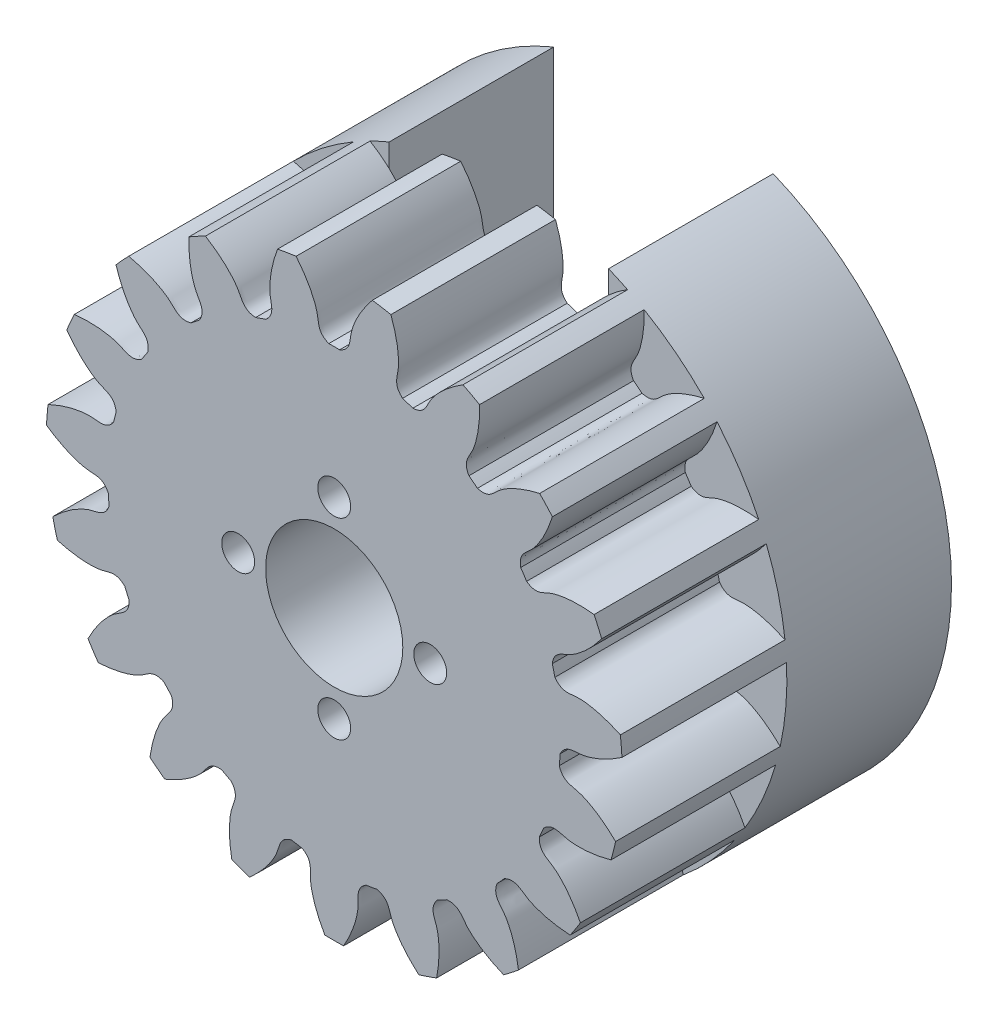
SolidWorks part; units mm, degrees
ref_plane "前视基准面" through (0, 0, 0) normal (0, 0, 1) x (1, 0, 0)
ref_plane "上视基准面" through (0, 0, 0) normal (0, 1, 0) x (1, 0, 0)
ref_plane "右视基准面" through (0, 0, 0) normal (1, 0, 0) x (0, 0, -1)
sketch "草图1" plane through (0, 0, 0) normal (0, 0, 1) x (1, 0, 0)
  circle A0 centre (0, 0) radius 52.5
extrude "凸台-拉伸1" add sketch "草图1" along normal blind 30
ref_axis "基准轴1" through (0, 0, -1.5) along (0, 0, 1)
sketch "草图2" plane through (0, 0, 0) normal (0, 0, 1) x (1, 0, 0)
  line L0 (0, 0) -> (0, 52.5) construction
  circle A0 centre (0, 0) radius 52.5 construction
  arc A1 (0.9829, 41.2383) -> (-0.9829, 41.2383) centre (0, 0) ccw
  arc A2 (15.3566, 59.3035) -> (-15.3566, 59.3035) centre (0, 0) ccw
  spline S0 degree 3 poles (0.9829, 41.2383) (3.0166, 42.0591) (2.7957, 43.6119) (3.1268, 45.1008) (3.1626, 45.2483) (3.206, 45.4123) (3.2575, 45.5925) (3.3179, 45.7888) (3.3877, 46.0008) (3.4677, 46.2282) (3.5584, 46.4706) (3.6606, 46.7278) (3.7749, 46.9994) (3.9017, 47.2849) (4.0419, 47.5841) (4.1959, 47.8963) (4.3643, 48.2213) (4.5477, 48.5586) (4.7466, 48.9076) (4.9617, 49.2679) (5.1933, 49.639) (5.4421, 50.0203) (5.7085, 50.4113) (5.993, 50.8115) (6.2961, 51.2203) (6.6182, 51.637) (6.9598, 52.0611) (7.3213, 52.492) (7.7031, 52.929) (8.1055, 53.3715) (8.529, 53.8189) (8.9739, 54.2704) (9.4405, 54.7254) (9.9291, 55.1832) (10.4401, 55.643) (10.9736, 56.1042) (11.53, 56.5661) (12.1095, 57.0279) (12.7123, 57.4888) (13.3386, 57.9482) (14.215, 58.5643) (14.8935, 59.0113) (15.3566, 59.3035) knots 0 0 0 0 0.181988 0.187669 0.194107 0.201302 0.209255 0.217965 0.227433 0.237658 0.248641 0.260381 0.272878 0.286133 0.300145 0.314915 0.330442 0.346727 0.363769 0.381568 0.400125 0.419439 0.43951 0.460339 0.481926 0.50427 0.527371 0.55123 0.575846 0.601219 0.62735 0.654238 0.681884 0.710287 0.739448 0.769366 0.800042 0.831474 0.863665 0.896612 0.930318 1 1 1 1
  spline S1 degree 3 poles (-0.9829, 41.2383) (-3.0166, 42.0591) (-2.7957, 43.6119) (-3.1268, 45.1008) (-3.1626, 45.2483) (-3.206, 45.4123) (-3.2575, 45.5925) (-3.3179, 45.7888) (-3.3877, 46.0008) (-3.4677, 46.2282) (-3.5584, 46.4706) (-3.6606, 46.7278) (-3.7749, 46.9994) (-3.9017, 47.2849) (-4.0419, 47.5841) (-4.1959, 47.8963) (-4.3643, 48.2213) (-4.5477, 48.5586) (-4.7466, 48.9076) (-4.9617, 49.2679) (-5.1933, 49.639) (-5.4421, 50.0203) (-5.7085, 50.4113) (-5.993, 50.8115) (-6.2961, 51.2203) (-6.6182, 51.637) (-6.9598, 52.0611) (-7.3213, 52.492) (-7.7031, 52.929) (-8.1055, 53.3715) (-8.529, 53.8189) (-8.9739, 54.2704) (-9.4405, 54.7254) (-9.9291, 55.1832) (-10.4401, 55.643) (-10.9736, 56.1042) (-11.53, 56.5661) (-12.1095, 57.0279) (-12.7123, 57.4888) (-13.3386, 57.9482) (-14.215, 58.5643) (-14.8935, 59.0113) (-15.3566, 59.3035) knots 0 0 0 0 0.181988 0.187669 0.194107 0.201302 0.209255 0.217965 0.227433 0.237658 0.248641 0.260381 0.272878 0.286133 0.300145 0.314915 0.330442 0.346727 0.363769 0.381568 0.400125 0.419439 0.43951 0.460339 0.481926 0.50427 0.527371 0.55123 0.575846 0.601219 0.62735 0.654238 0.681884 0.710287 0.739448 0.769366 0.800042 0.831474 0.863665 0.896612 0.930318 1 1 1 1
extrude "切除-拉伸1" cut sketch "草图2" along normal through all
pattern_circular "阵列(圆周)1" count 19 every 18.947 about axis through (0, 0, -1.5) along (0, 0, 1) of "切除-拉伸1"
sketch "草图3" plane through (0, 0, 0) normal (0, 0, 1) x (1, 0, 0)
  circle A0 centre (0, 0) radius 47.5 construction
  dimension "Dn" = 95
sketch "草图5" plane through (0, 0, 30) normal (0, 0, 1) x (1, 0, 0)
  circle A0 centre (0, 0) radius 12.5
extrude "切除-拉伸2" cut sketch "草图5" against normal blind 30
sketch "草图6" plane through (0, 0, 30) normal (0, 0, 1) x (1, 0, 0)
  circle A0 centre (0, 0) radius 17.5
  circle A1 centre (-17.5, 0) radius 3
extrude "切除-拉伸3" cut sketch "草图6" against normal blind 30 contours A0 A1 | A0 A1 region at (-16.1816, 0, 30) region at (-18.7258, 0, 30)
pattern_circular "阵列(圆周)2" count 4 over 360 about axis through (0, 0, 0) along (0, 0, 1) of "切除-拉伸3"
sketch "草图7" plane through (0, 0, 0) normal (0, 0, -1) x (-1, 0, 0)
  circle A0 centre (0, 0) radius 52.5
extrude "凸台-拉伸2" add sketch "草图7" along normal blind 30
sketch "草图8" plane through (0, 0, -30) normal (0, 0, -1) x (-1, 0, 0)
  line L1 (-20, 63.8599) -> (20, 63.8599)
  line L2 (-20, 63.8599) -> (-20, -63.8599)
  line L3 (-20, -63.8599) -> (20, -63.8599)
  line L4 (20, 63.8599) -> (20, -63.8599)
  line L5 (-20, 63.8599) -> (20, -63.8599) construction
  line L6 (-20, -63.8599) -> (20, 63.8599) construction
  circle A0 centre (0, 0) radius 12.5
  circle M6 centre (0, 0) radius 52.5
  dimension "D1" = 40
extrude "切除-拉伸4" cut sketch "草图8" against normal blind 30 contours A0 | L4 L2 A0 M6 | L4 L1 L2 M6 | A0 | L2 L1 L4 L3 region at (0, 57.4761, -30) region at (0, 51.3764, -30) region at (0, 0, -30)
